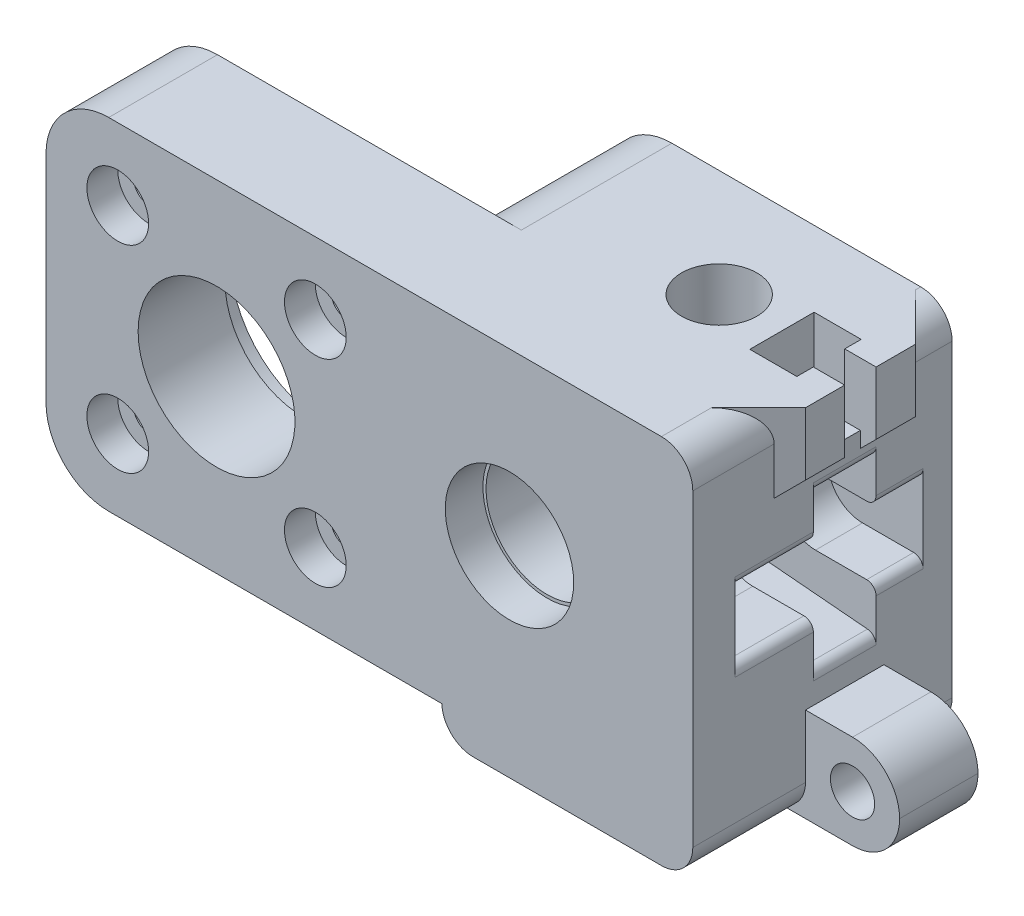
SolidWorks part; units mm, degrees
ref_plane "Front Plane" through (0, 0, 0) normal (0, 0, 1) x (1, 0, 0)
ref_plane "Top Plane" through (0, 0, 0) normal (0, 1, 0) x (1, 0, 0)
ref_plane "Right Plane" through (0, 0, 0) normal (1, 0, 0) x (0, 0, -1)
sketch "Sketch1" plane through (0, 0, 0) normal (0, 0, 1) x (1, 0, 0)
  line L0 (0, 0) -> (-23.7236, 0)
  line L3 (-33.7236, 10) -> (-13.7236, 10)
  line L4 (-33.7236, 10) -> (-33.7236, -10)
  line L5 (-33.7236, -10) -> (-13.7236, -10)
  line L6 (-13.7236, 10) -> (-13.7236, -10)
  line L7 (-33.7236, 10) -> (-13.7236, -10) construction
  line L8 (-33.7236, -10) -> (-13.7236, 10) construction
  circle A0 centre (0, 0) radius 5
  circle A2 centre (-23.7236, 0) radius 7.5
  circle A3 centre (0, 0) radius 4.445
  circle A4 centre (0, 0) radius 3.81
  dimension "D1" = 10
  dimension "D5" = 15
  dimension "D2" = 23.7236
  dimension "D6" = 20
  dimension "D7" = 20
sketch "Sketch2" plane through (0, 0, 0) normal (0, 0, 1) x (1, 0, 0)
  line L0 (5.56, 19.4528) -> (5.56, -19.4528)
  line L2 (0, 0) -> (-23.7236, 0)
  line L3 (3.81, 19.4528) -> (3.81, -19.4528)
  line L4 (5.56, 13.8098) -> (5.56, -13.8098) construction
  line L5 (3.81, 13.8098) -> (3.81, -13.8098) construction
  line L6 (3.81, -11.2738) -> (5.56, -11.2738)
  line L7 (3.81, 13.08) -> (5.56, 13.08)
  line L8 (-1.665, -10.08) -> (11.035, -10.08)
  line L9 (-1.665, -10.08) -> (-1.665, -12.4676)
  line L10 (-1.665, -12.4676) -> (11.035, -12.4676)
  line L11 (11.035, -10.08) -> (11.035, -12.4676)
  line L12 (-1.665, -10.08) -> (11.035, -12.4676) construction
  line L13 (-1.665, -12.4676) -> (11.035, -10.08) construction
  line L15 (1.685, 16.08) -> (7.685, 16.08)
  line L16 (1.685, 16.08) -> (1.685, 10.08)
  line L17 (1.685, 10.08) -> (7.685, 10.08)
  line L18 (7.685, 16.08) -> (7.685, 10.08)
  line L19 (1.685, 16.08) -> (7.685, 10.08) construction
  line L20 (1.685, 10.08) -> (7.685, 16.08) construction
  circle A1 centre (0, 0) radius 5 construction
  circle A2 centre (0, 0) radius 3.81 construction
  point P19 (4.685, -11.2738)
  point P20 (4.685, -11.2738)
  point P25 (0, -5)
  point P30 (4.685, 13.08)
  point P31 (4.685, 13.08)
  point P36 (0, 5)
  dimension "D1" = 1.75
  dimension "D2" = 2.3876
  dimension "D3" = 12.7
  dimension "D4" = 5.08
  dimension "D5" = 6
  dimension "D6" = 5.08
sketch "Sketch5" plane through (0, 0, 0) normal (0, 0, 1) x (1, 0, 0)
  line L6 (-37.5336, 13.81) -> (12.62, 13.81)
  line L7 (-37.5336, 13.81) -> (-37.5336, -13.81)
  line L8 (-37.5336, -13.81) -> (12.62, -13.81)
  line L9 (-9.9136, 13.81) -> (-37.5336, 13.81)
  line L10 (-9.9136, -13.81) -> (-9.9136, 13.81)
  line L11 (-37.5336, -13.81) -> (-9.9136, -13.81)
  line L12 (-37.5336, 13.81) -> (-37.5336, -13.81)
  line L13 (-9.9136, 13.81) -> (-37.5336, 13.81) construction
  line L14 (-9.9136, -13.81) -> (-9.9136, 13.81) construction
  line L15 (-37.5336, -13.81) -> (-9.9136, -13.81) construction
  line L16 (-37.5336, 13.81) -> (-37.5336, -13.81) construction
  line L17 (12.62, 13.81) -> (12.62, -13.81)
  circle A1 centre (0, 0) radius 12.62 construction
  circle A2 centre (0, 0) radius 8.81
  circle A3 centre (0, 0) radius 8.81 construction
  dimension "D1" = 3.81
  dimension "D2" = 3.81
  dimension "D3" = 3.81
extrude "Boss-Extrude1" add sketch "Sketch5" along normal blind 21
sketch "Sketch6" plane through (0, 0, 0) normal (0, 0, -1) x (-1, 0, 0)
  circle A0 centre (0, 0) radius 5 construction
  circle A1 centre (0, 0) radius 5.2
  dimension "D1" = 10
  dimension "D2" = 0.2
extrude "Cut-Extrude1" cut sketch "Sketch6" against normal blind 4
sketch "Sketch7" plane through (0, 0, 4) normal (0, 0, -1) x (-1, 0, 0)
  circle A0 centre (0, 0) radius 4.75 construction
  circle A1 centre (0, 0) radius 4.95
  dimension "D1" = 9.5
  dimension "D2" = 0.2
extrude "Cut-Extrude2" cut sketch "Sketch7" against normal through all
sketch "Sketch8" plane through (0, 0, 21) normal (0, 0, 1) x (1, 0, 0)
  circle A0 centre (0, 0) radius 5 construction
  circle A1 centre (0, 0) radius 5.2
  dimension "D1" = 10
  dimension "D2" = 0.2
extrude "Cut-Extrude3" cut sketch "Sketch8" against normal blind 3.048
sketch "Sketch11" plane through (0, 0, 0) normal (0, 0, -1) x (-1, 0, 0)
  line L0 (1.665, -12.4676) -> (-11.035, -12.4676) construction
  line L1 (-11.035, -10.08) -> (-11.035, -12.4676) construction
  line L2 (1.665, -10.08) -> (-11.035, -10.08) construction
  line L3 (1.665, -10.08) -> (1.665, -12.4676) construction
  line L4 (1.665, -12.4676) -> (-11.035, -12.4676) construction
  line L5 (-11.035, -10.08) -> (-11.035, -12.4676) construction
  line L6 (1.665, -10.08) -> (-11.035, -10.08) construction
  line L7 (1.665, -10.08) -> (1.665, -12.4676) construction
  line L8 (-14.845, -10.08) -> (-14.845, -16.2776)
  line L9 (5.475, -16.2776) -> (-14.845, -16.2776)
  line L10 (5.475, -10.08) -> (5.475, -16.2776)
  line L11 (-14.845, -10.08) -> (5.475, -10.08)
  dimension "D1" = 3.81
extrude "Boss-Extrude2" add sketch "Sketch11" against normal up to surface (21 mm away) up to face at (5.2, 0, 21)
sketch "Sketch9" plane through (0, -13.81, 0) normal (0, -1, 0) x (1, 0, 0)
  line L0 (4.685, 0) -> (4.685, 21) construction
  line L1 (-37.5336, 21) -> (-5.475, 21) construction
  circle A0 centre (4.685, 8.699) radius 1.143
  point P5 (4.685, 4)
  point P6 (4.685, 7.556)
  point P9 (4.685, 7.556)
  dimension "D3" = 2.286
  dimension "D1" = 4
  dimension "D2" = 3.556
extrude "Cut-Extrude4" cut sketch "Sketch9" against normal through all and the other way through all
ref_axis "Axis1" through (4.685, 13.81, 8.699) along (0, -1, 0)
ref_plane "Plane1" through (0, 0, 8.699) normal (0, 0, -1) x (-1, 0, 0)
ref_plane "Plane2" through (0, 0, 15.2522) normal (0, 0, -1) x (-1, 0, 0)
sketch "Sketch12" plane through (0, 0, 0) normal (0, 0, -1) x (-1, 0, 0)
  line L1 (-11.289, -9.8133) -> (1.919, -9.8133)
  line L2 (-11.289, -9.8133) -> (-11.289, -12.7343)
  line L3 (-11.289, -12.7343) -> (1.919, -12.7343)
  line L4 (1.919, -9.8133) -> (1.919, -12.7343)
  line L5 (-11.289, -9.8133) -> (1.919, -12.7343) construction
  line L6 (-11.289, -12.7343) -> (1.919, -9.8133) construction
  point P0 (-4.685, -11.2738)
  dimension "D1" = 13.208
  dimension "D2" = 2.921
extrude "Cut-Extrude5" cut sketch "Sketch12" against normal up to surface (15.2522 mm away) up to plane "Plane2"
sketch "Sketch13" plane through (0, -16.2776, 0) normal (0, -1, 0) x (1, 0, 0)
  circle A0 centre (4.685, 8.699) radius 4.7625 construction
  circle A1 centre (4.685, 8.699) radius 4.9403
  dimension "D1" = 9.525
  dimension "D2" = 0.1778
extrude "Cut-Extrude6" cut sketch "Sketch13" against normal blind 8.89
sketch "Sketch14" plane through (0, 13.81, 0) normal (0, 1, 0) x (1, 0, 0)
  circle A0 centre (4.685, -8.699) radius 3.048
  dimension "D1" = 6.096
extrude "Cut-Extrude7" cut sketch "Sketch14" against normal blind 6.35
sketch "Sketch15" plane through (0, 0, 0) normal (0, 0, -1) x (-1, 0, 0)
  line L0 (12.9286, 10.795) -> (12.9286, 13.81)
  line L1 (12.9286, 10.795) -> (34.5186, 10.795) construction
  line L2 (12.9286, 10.795) -> (12.9286, -10.795) construction
  line L3 (12.9286, -10.795) -> (34.5186, -10.795) construction
  line L4 (34.5186, 10.795) -> (34.5186, -10.795) construction
  line L5 (12.9286, 10.795) -> (34.5186, -10.795) construction
  line L6 (12.9286, -10.795) -> (34.5186, 10.795) construction
  line L8 (-12.62, 13.81) -> (37.5336, 13.81) construction
  line L9 (12.9286, 13.81) -> (37.5336, 13.81)
  line L10 (37.5336, 13.81) -> (37.5336, -13.81)
  line L11 (37.5336, -13.81) -> (12.9286, -13.81)
  line L12 (37.5336, -13.81) -> (5.475, -13.81) construction
  line L13 (12.9286, -13.81) -> (12.9286, 10.795)
  point P0 (23.7236, 0)
  dimension "D1" = 21.59
extrude "Cut-Extrude8" cut sketch "Sketch15" against normal blind 12.192
sketch "Sketch16" plane through (0, 0, 12.192) normal (0, 0, -1) x (-1, 0, 0)
  circle A0 centre (23.7236, 0) radius 7.5 construction
  circle A1 centre (23.7236, 0) radius 7.6778
  dimension "D1" = 15
  dimension "D2" = 0.1778
extrude "Cut-Extrude9" cut sketch "Sketch16" against normal blind 1.778
sketch "Sketch17" plane through (0, 0, 13.97) normal (0, 0, -1) x (-1, 0, 0)
  circle A0 centre (23.7236, 0) radius 6.35
  dimension "D1" = 12.7
extrude "Cut-Extrude10" cut sketch "Sketch17" against normal through all
sketch "Sketch18" plane through (0, 0, 12.192) normal (0, 0, -1) x (-1, 0, 0)
  line L0 (33.7236, -10) -> (13.7236, 10) construction
  line L1 (15.7236, 8) -> (31.7236, 8) construction
  line L2 (15.7236, 8) -> (15.7236, -8) construction
  line L3 (15.7236, -8) -> (31.7236, -8) construction
  line L4 (31.7236, 8) -> (31.7236, -8) construction
  line L5 (15.7236, 8) -> (31.7236, -8) construction
  line L6 (15.7236, -8) -> (31.7236, 8) construction
  circle A0 centre (15.7236, 8) radius 1.2
  circle A1 centre (31.7236, 8) radius 1.2
  circle A2 centre (31.7236, -8) radius 1.2
  circle A3 centre (15.7236, -8) radius 1.2
  point P0 (23.7236, 0)
  dimension "D2" = 2.4
  dimension "D3" = 2.4
  dimension "D4" = 2.4
  dimension "D5" = 2.4
  dimension "D1" = 16
extrude "Cut-Extrude11" cut sketch "Sketch18" against normal through all
sketch "Sketch19" plane through (0, -10.08, 0) normal (0, 1, 0) x (1, 0, 0)
  line L4 (12.62, 0) -> (12.62, -21)
  line L5 (12.62, -21) -> (14.845, -21)
  line L6 (14.845, -21) -> (14.845, 0)
  line L7 (14.845, 0) -> (12.62, 0)
  line L8 (12.62, 0) -> (12.62, -21)
  line L9 (12.62, -21) -> (14.845, -21)
  line L10 (14.845, -21) -> (14.845, 0)
  line L11 (14.845, 0) -> (12.62, 0)
  dimension "D1" = 0
extrude "Boss-Extrude3" add sketch "Sketch19" along normal up to surface (23.89 mm away) up to face at (1.637, 13.81, 8.699)
ref_axis "Axis2" through (0, 0, 17.952) along (0, 0, -1)
ref_plane "Plane3" through (0, 0, 0) normal (1, 0, 0) x (0, 0, -1)
sketch "Sketch20" plane through (0, 0, 0) normal (1, 0, 0) x (0, 0, -1)
  line L0 (-17.952, 0) -> (-4, 0) construction
  line L1 (-11.239, 4.9505) -> (-6.159, 4.9505)
  line L2 (-11.239, 4.9505) -> (-11.239, -4.9505)
  line L3 (-11.239, -4.9505) -> (-6.159, -4.9505)
  line L4 (-6.159, 4.9505) -> (-6.159, -4.9505)
  line L5 (-11.239, 4.9505) -> (-6.159, -4.9505) construction
  line L6 (-11.239, -4.9505) -> (-6.159, 4.9505) construction
  line L7 (-8.699, 13.81) -> (-8.699, -16.2776) construction
  point P0 (-8.699, 0)
  dimension "D1" = 5.08
  dimension "D2" = 9.9009
extrude "Cut-Extrude12" cut sketch "Sketch20" along normal through all
sketch "Sketch22" plane through (0, 0, 11.239) normal (0, 0, -1) x (-1, 0, 0)
  line L0 (0, 4.9505) -> (-17.4212, 6.4746)
  line L1 (0, 0) -> (-21.6296, 0) construction
  line L2 (0, -4.9505) -> (-17.4212, -6.4746)
  line L3 (-17.4212, 6.4746) -> (-17.4212, -6.4746)
  line L4 (0, -4.9505) -> (0, 4.9505)
  dimension "D1" = 5
  dimension "D2" = 9.9009
extrude "Cut-Extrude13" cut sketch "Sketch22" along normal up to surface (5.08 mm away) up to face at (5.7733, 0, 6.159)
sketch "Sketch23" plane through (14.845, 0, 0) normal (1, 0, 0) x (0, 0, -1)
  line L0 (0, 13.81) -> (-21, 13.81) construction
  line L1 (-13.144, 8.73) -> (-4.254, 8.73)
  line L2 (-13.144, 8.73) -> (-13.144, 13.81)
  line L3 (-13.144, 13.81) -> (-4.254, 13.81)
  line L4 (-4.254, 8.73) -> (-4.254, 13.81)
  line L5 (-8.699, -6.2492) -> (-8.699, 6.2492) construction
  line L6 (-6.159, -6.2492) -> (-11.239, -6.2492) construction
  point P6 (-8.699, 8.73)
  dimension "D1" = 8.89
  dimension "D2" = 5.08
extrude "Boss-Extrude4" add sketch "Sketch23" along normal blind 1.27
sketch "Sketch25" plane through (0, 0, 11.239) normal (0, 0, 1) x (1, 0, 0)
  line L0 (4.685, 7.46) -> (4.685, -7.3876) construction
  line L1 (7.733, 7.46) -> (1.637, 7.46) construction
  line L2 (-0.2553, -7.3876) -> (9.6253, -7.3876) construction
  line L3 (4.939, 7.46) -> (4.939, -7.3876) construction
  line L4 (0, 0) -> (19.7355, 0) construction
  line L5 (9.939, 2.5) -> (16.732, 2.5) construction
  line L6 (16.732, 2.5) -> (16.732, -2.5) construction
  line L7 (16.732, -2.5) -> (9.939, -2.5) construction
  line L8 (9.939, 2.754) -> (16.986, 2.754)
  line L9 (16.986, 2.754) -> (16.986, -2.754)
  line L10 (16.986, -2.754) -> (9.939, -2.754)
  circle A0 centre (9.939, 0) radius 5 construction
  arc A1 (9.939, 2.5) -> (9.939, -2.5) centre (9.939, 0) ccw construction
  arc A2 (9.939, 2.754) -> (9.939, -2.754) centre (9.939, 0) ccw
  dimension "D2" = 10
  dimension "D3" = 5
  dimension "D1" = 0.254
  dimension "D4" = 0.254
extrude "Cut-Extrude15" cut sketch "Sketch25" along normal blind 6.35
sketch "Sketch26" plane through (0, 0, 6.159) normal (0, 0, 1) x (1, 0, 0)
  line L0 (16.986, 2.754) -> (16.986, -2.754) construction
  line L1 (16.986, 2.754) -> (16.986, -2.754)
  line L2 (9.939, 2.754) -> (16.986, 2.754) construction
  line L3 (9.939, 2.754) -> (16.986, 2.754)
  line L4 (16.986, -2.754) -> (9.939, -2.754) construction
  line L5 (0, -4.95) -> (0, -4.9505)
  line L6 (0, -4.9505) -> (14.845, -6.2492)
  line L7 (14.845, -6.2492) -> (14.845, 6.2492)
  line L8 (14.845, 6.2492) -> (0, 4.9505)
  line L9 (0, 4.9505) -> (0, 4.95)
  line L10 (0, -4.95) -> (0, -4.9505)
  line L11 (0, -4.9505) -> (14.845, -6.2492)
  line L12 (14.845, -6.2492) -> (14.845, 6.2492)
  line L13 (14.845, 6.2492) -> (0, 4.9505)
  line L14 (0, 4.9505) -> (0, 4.95)
  line L15 (16.986, -2.754) -> (9.939, -2.754)
  arc A0 (9.939, 2.754) -> (9.939, -2.754) centre (9.939, 0) ccw construction
  arc A1 (0, -4.95) -> (0, 4.95) centre (0, 0) ccw
  arc A2 (0, -4.95) -> (0, 4.95) centre (0, 0) ccw
  arc A3 (9.939, 2.754) -> (9.939, -2.754) centre (9.939, 0) ccw
  dimension "D1" = 0
extrude "Cut-Extrude16" cut sketch "Sketch26" against normal blind 3.81 contours L1 L15 A3 L3
sketch "Sketch27" plane through (14.845, 0, 0) normal (1, 0, 0) x (0, 0, -1)
  line L0 (-8.699, 8.73) -> (-8.699, -16.2776) construction
  line L1 (-13.144, 8.73) -> (-4.254, 8.73) construction
  line L2 (-21, -16.2776) -> (0, -16.2776) construction
  line L3 (-11.874, -16.2776) -> (-5.524, -16.2776)
  line L4 (-5.524, -16.2776) -> (-5.524, -8.6576)
  line L5 (-5.524, -8.6576) -> (-11.874, -8.6576)
  line L6 (-11.874, -16.2776) -> (-11.874, -8.6576)
  point P10 (-8.699, -8.6576)
  dimension "D1" = 6.35
  dimension "D2" = 7.62
extrude "Boss-Extrude6" add sketch "Sketch27" along normal blind 7.62
chamfer "Chamfer1" distance 1.27 angle 45 3 edges at (14.845, 8.73, 8.699)
fillet "Fillet2" radius 3.81 2 edges at (22.465, -16.2776, 8.699) (22.465, -8.6576, 8.699)
sketch "Sketch28" plane through (0, 13.81, 0) normal (0, 1, 0) x (1, 0, 0)
  line L0 (4.685, -8.699) -> (16.115, -8.699) construction
  line L1 (16.115, -4.254) -> (16.115, -13.144) construction
  line L3 (9.765, -11.3025) -> (13.575, -11.3025)
  line L4 (9.765, -11.3025) -> (9.765, -6.0955)
  line L5 (9.765, -6.0955) -> (13.575, -6.0955)
  line L6 (13.575, -11.3025) -> (13.575, -6.0955)
  line L7 (9.765, -11.3025) -> (13.575, -6.0955) construction
  line L8 (9.765, -6.0955) -> (13.575, -11.3025) construction
  point P5 (11.67, -8.699)
  dimension "D1" = 3.81
  dimension "D2" = 5.207
  dimension "D3" = 2.54
extrude "Cut-Extrude17" cut sketch "Sketch28" against normal blind 5.08
sketch "Sketch29" plane through (13.575, 0, 0) normal (-1, 0, 0) x (0, 0, 1)
  line L0 (8.699, 13.81) -> (8.699, 8.73) construction
  line L1 (9.969, 8.73) -> (9.969, 13.81)
  line L2 (7.429, 8.73) -> (7.429, 13.81)
  line L3 (9.969, 8.73) -> (7.429, 8.73)
  line L4 (11.3025, 13.81) -> (6.0955, 13.81)
  line L5 (6.0955, 13.81) -> (6.0955, 8.73)
  line L6 (6.0955, 8.73) -> (11.3025, 8.73)
  line L7 (11.3025, 8.73) -> (11.3025, 13.81)
  line L8 (11.3025, 13.81) -> (6.0955, 13.81) construction
  line L9 (6.0955, 13.81) -> (6.0955, 8.73) construction
  line L10 (6.0955, 8.73) -> (11.3025, 8.73) construction
  line L11 (11.3025, 8.73) -> (11.3025, 13.81) construction
  line L12 (9.969, 13.81) -> (7.429, 13.81)
  dimension "D2" = 2.54
  dimension "D1" = 0
extrude "Cut-Extrude18" cut sketch "Sketch29" against normal blind 5.08
sketch "Sketch30" plane through (0, 0, 11.874) normal (0, 0, 1) x (1, 0, 0)
  circle A0 centre (18.655, -12.4676) radius 1.7907
  dimension "D1" = 3.5814
extrude "Cut-Extrude19" cut sketch "Sketch30" against normal through all
sketch "Sketch31" plane through (14.845, 0, 0) normal (1, 0, 0) x (0, 0, -1)
  line L0 (-9.969, 8.73) -> (-7.429, 8.73)
  line L1 (-7.429, 8.73) -> (-7.429, 7.1035)
  line L2 (-7.429, 7.1035) -> (-9.969, 7.1035)
  line L3 (-9.969, 7.1035) -> (-9.969, 8.73)
extrude "Cut-Extrude20" cut sketch "Sketch31" along normal through all
fillet "Fillet3" radius 0.508 1 edges at (3.542, 7.46, 8.699)
sketch "Sketch32" plane through (0, 0, 21) normal (0, 0, 1) x (1, 0, 0)
  circle A0 centre (-15.7236, 8) radius 2.5
  circle A1 centre (-31.7236, 8) radius 2.5
  circle A2 centre (-31.7236, -8) radius 2.5
  circle A3 centre (-15.7236, -8) radius 2.5
  dimension "D1" = 5
  dimension "D2" = 5
  dimension "D3" = 5
  dimension "D4" = 5
extrude "Cut-Extrude21" cut sketch "Sketch32" against normal blind 2.5
fillet "Fillet4" radius 5.08 2 edges at (-37.5336, -13.81, 16.596) (-37.5336, 13.81, 16.596)
fillet "Fillet5" radius 5.08 2 edges at (-12.9286, -13.81, 6.096) (-12.9286, 13.81, 6.096)
fillet "Fillet6" radius 2.54 4 edges at (14.845, -16.2776, 16.437) (14.845, -16.2776, 2.762)
fillet "Fillet7" radius 2.54 1 edges at (-5.475, -16.2776, 10.5)
fillet "Fillet8" radius 0.762 2 edges at (14.845, 6.2492, 8.699) (14.845, -6.2492, 8.699)
fillet "Fillet9" radius 0.762 4 edges at (14.845, 2.754, 4.254) (14.845, -2.754, 4.254) (14.845, 2.754, 14.414) (14.845, -2.754, 14.414)
